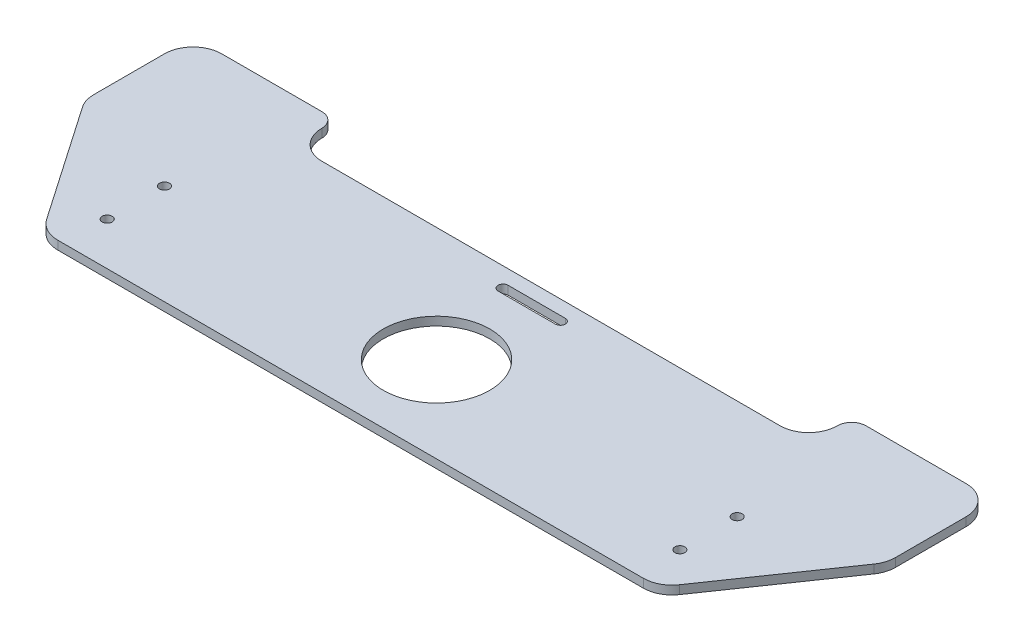
SolidWorks part; units mm, degrees
ref_plane "前视基准面" through (0, 0, 0) normal (0, 0, 1) x (1, 0, 0)
ref_plane "上视基准面" through (0, 0, 0) normal (0, 1, 0) x (1, 0, 0)
ref_plane "右视基准面" through (0, 0, 0) normal (1, 0, 0) x (0, 0, -1)
other "Configuration Table"
sketch "草图1" plane through (0, 0, 0) normal (0, 1, 0) x (1, 0, 0)
  line L0 (-138.2358, 19.5134) -> (-110.4921, -20.7712)
  line L2 (-140, 25.1854) -> (-140, 65)
  line L3 (-130.0992, 74.9008) -> (-100, 74.9008)
  line L5 (-200, -75) -> (0, 0) construction
  line L6 (-140, 74.9008) -> (0, 0) construction
  line L8 (-90, 64.9008) -> (-90, 54.9008)
  line L9 (-80, 44.9008) -> (80, 44.9008)
  line L12 (0, 0) -> (0, 50000) construction
  line L13 (-102.2563, -25.0992) -> (102.2563, -25.0992)
  line L15 (140, 74.9008) -> (0, 0) construction
  line L16 (200, -75) -> (0, 0) construction
  line L17 (90, 64.9008) -> (90, 54.9008)
  line L18 (130.0992, 74.9008) -> (100, 74.9008)
  line L19 (140, 25.1854) -> (140, 65)
  line L20 (138.2358, 19.5134) -> (110.4921, -20.7712)
  arc A2 (-90, 54.9008) -> (-80, 44.9008) centre (-80, 54.9008) ccw
  arc A3 (-90, 64.9008) -> (-100, 74.9008) centre (-100, 64.9008) ccw
  arc A5 (-140, 65) -> (-130.0992, 74.9008) centre (-130.0992, 65) cw
  arc A8 (-138.2358, 19.5134) -> (-140, 25.1854) centre (-130, 25.1854) cw
  arc A9 (-110.4921, -20.7712) -> (-102.2563, -25.0992) centre (-102.2563, -15.0992) ccw
  arc A10 (110.4921, -20.7712) -> (102.2563, -25.0992) centre (102.2563, -15.0992) cw
  arc A11 (138.2358, 19.5134) -> (140, 25.1854) centre (130, 25.1854) ccw
  arc A12 (140, 65) -> (130.0992, 74.9008) centre (130.0992, 65) ccw
  arc A13 (90, 64.9008) -> (100, 74.9008) centre (100, 64.9008) cw
  arc A14 (90, 54.9008) -> (80, 44.9008) centre (80, 54.9008) cw
  point P0 (0, 0)
  point P14 (0, 25)
  point P40 (0, 44.9008)
  point P41 (0, -25.0992)
  dimension "D4" = 50
  dimension "D1" = 280
  dimension "D2" = 100
  dimension "D3" = 30
extrude "凸台-拉伸1" add sketch "草图1" along normal blind 3
sketch "草图4" plane through (0, 3, 0) normal (0, 1, 0) x (1, 0, 0)
  line L0 (140, 25.1854) -> (140, 65) construction
  line L1 (140, 59.9008) -> (-147.1078, 59.9008)
  line L2 (140, 59.9008) -> (140, 79.3217)
  line L3 (140, 79.3217) -> (-147.1078, 79.3217)
  line L4 (-147.1078, 59.9008) -> (-147.1078, 79.3217)
  line L5 (-102.2563, -25.0992) -> (102.2563, -25.0992) construction
  dimension "D1" = 85
extrude "切除-拉伸2" cut sketch "草图4" against normal blind 18
fillet "圆角3" radius 5 2 edges at (-90, 1.5, -59.9008) (90, 1.5, -59.9008)
fillet "圆角4" radius 10 2 edges at (140, 1.5, -59.9008) (-140, 1.5, -59.9008)
sketch "草图5" plane through (0, 3, 0) normal (0, 1, 0) x (1, 0, 0)
  circle A0 centre (100, -10.0992) radius 1.75
  circle A1 centre (100, 9.9008) radius 1.75
  circle A2 centre (-100, -10.0992) radius 1.75
  circle A3 centre (-100, 9.9008) radius 1.75
extrude "切除-拉伸3" cut sketch "草图5" against normal blind 18
sketch "草图8" plane through (0, 3, 0) normal (0, 1, 0) x (1, 0, 0)
  line L0 (-10, 38.1508) -> (10, 38.1508) construction
  line L1 (-10, 39.9008) -> (10, 39.9008)
  line L2 (-10, 36.4008) -> (10, 36.4008)
  line L3 (80, 44.9008) -> (-80, 44.9008) construction
  arc A0 (-10, 39.9008) -> (-10, 36.4008) centre (-10, 38.1508) ccw
  arc A1 (10, 36.4008) -> (10, 39.9008) centre (10, 38.1508) ccw
  point P2 (0, 38.1508)
  dimension "D1" = 1.75
  dimension "D2" = 20
  dimension "D3" = 5
extrude "切除-拉伸6" cut sketch "草图8" against normal blind 3
sketch "草图9" plane through (0, 0, 0) normal (0, -1, 0) x (1, 0, 0)
  circle A0 centre (0, -4.9119) radius 18.5881
extrude "切除-拉伸7" cut sketch "草图9" against normal blind 10
